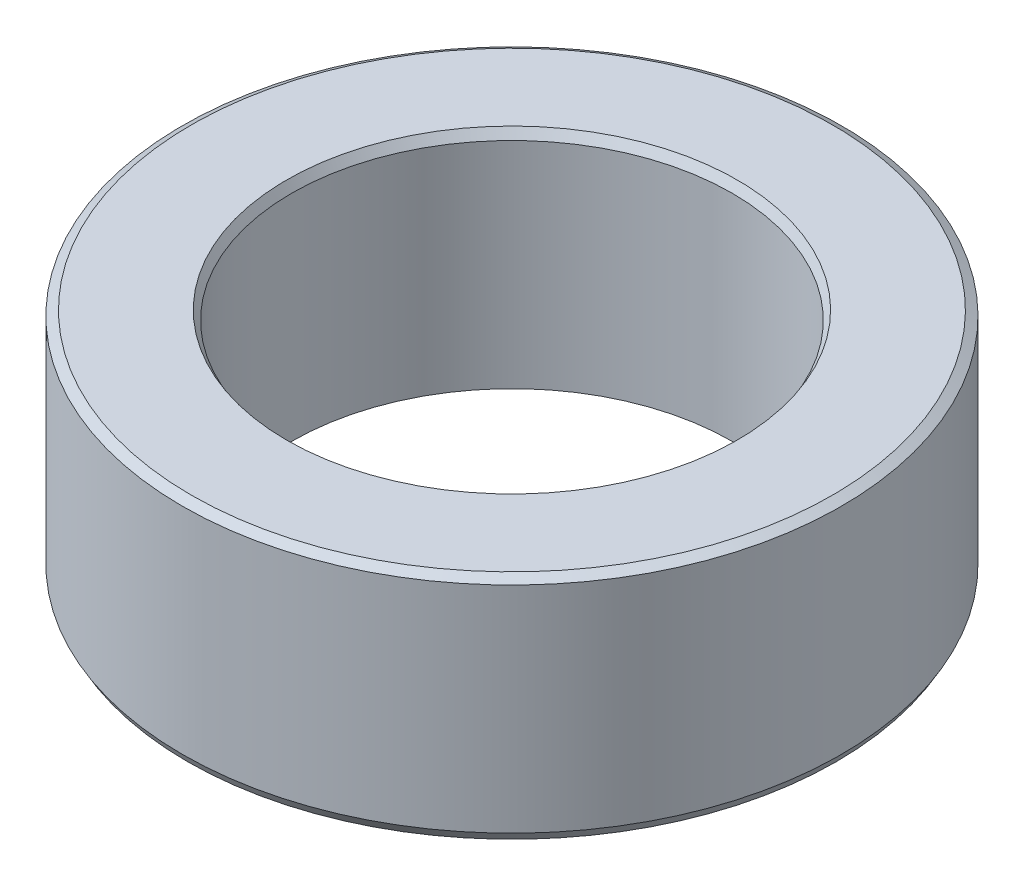
SolidWorks part; units mm, degrees
ref_plane "Front Plane" through (0, 0, 0) normal (0, 0, 1) x (1, 0, 0)
ref_plane "Top Plane" through (0, 0, 0) normal (0, 1, 0) x (1, 0, 0)
ref_plane "Right Plane" through (0, 0, 0) normal (1, 0, 0) x (0, 0, -1)
sketch "Sketch1" plane through (0, 0, 0) normal (0, 1, 0) x (1, 0, 0)
  circle A0 centre (0, 0) radius 32.5
  dimension "SLEEVE_OD" = 65
extrude "Boss-Extrude1" add sketch "Sketch1" along normal blind 22.5777
sketch "Sketch2" plane through (0, 0, 0) normal (0, 1, 0) x (1, 0, 0)
  circle A0 centre (0, 0) radius 21.7154
  dimension "BORE_D" = 43.4309
extrude "Cut-Extrude1" cut sketch "Sketch2" along normal through all
chamfer "Chamfer1" distance 0.5061 angle 60 4 edges at (0, 22.5777, 21.7154) (0, 0, 21.7154) (0, 0, 32.5) (0, 22.5777, 32.5) first distance on face at (0, 22.5777, 21.7154) first distance on face at (0, 0, 21.7154) first distance on face at (0, 22.5777, 32.5)
